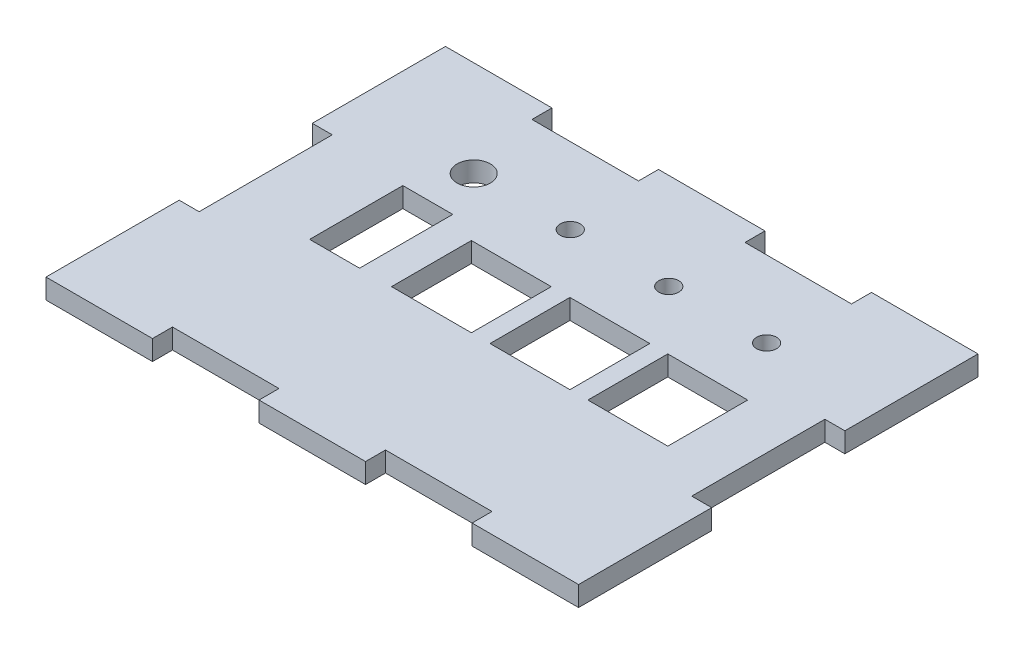
SolidWorks part; units mm, degrees
ref_plane "Front Plane" through (0, 0, 0) normal (0, 0, 1) x (1, 0, 0)
ref_plane "Top Plane" through (0, 0, 0) normal (0, 1, 0) x (1, 0, 0)
ref_plane "Right Plane" through (0, 0, 0) normal (1, 0, 0) x (0, 0, -1)
sketch "Top and Bottom" plane through (0, 0, 0) normal (0, 1, 0) x (1, 0, 0)
  line L0 (32, 60) -> (48, 60)
  line L1 (0, 0) -> (16, 0)
  line L2 (0, 0) -> (0, 20)
  line L3 (0, 60) -> (16, 60)
  line L4 (80, 0) -> (80, 20)
  line L5 (64, 60) -> (80, 60)
  line L6 (16, 60) -> (16, 57)
  line L7 (16, 57) -> (32, 57)
  line L8 (32, 60) -> (32, 57)
  line L9 (42, 36.7) -> (54, 36.7)
  line L10 (48, 60) -> (48, 57)
  line L11 (48, 57) -> (64, 57)
  line L12 (64, 60) -> (64, 57)
  line L13 (27.2, 36.7) -> (39.2, 36.7)
  line L14 (64, 0) -> (64, 3)
  line L15 (48, 3) -> (64, 3)
  line L16 (48, 0) -> (48, 3)
  line L17 (32, 0) -> (32, 3)
  line L18 (16, 0) -> (16, 3)
  line L19 (16, 3) -> (32, 3)
  line L20 (64, 0) -> (80, 0)
  line L21 (32, 0) -> (48, 0)
  line L22 (0, 40) -> (0, 60)
  line L23 (0, 40) -> (3, 40)
  line L24 (80, 40) -> (77, 40)
  line L25 (0, 20) -> (3, 20)
  line L26 (3, 40) -> (3, 20)
  line L27 (77, 40) -> (77, 20)
  line L28 (80, 20) -> (77, 20)
  line L29 (80, 40) -> (80, 60)
  line L30 (27.2, 36.7) -> (27.2, 24.7)
  line L31 (27.2, 24.7) -> (39.2, 24.7)
  line L32 (39.2, 36.7) -> (39.2, 24.7)
  line L33 (42, 36.7) -> (42, 24.7)
  line L34 (42, 24.7) -> (54, 24.7)
  line L35 (54, 36.7) -> (54, 24.7)
  line L36 (56.7, 36.7) -> (68.7, 36.7)
  line L37 (56.7, 36.7) -> (56.7, 24.7)
  line L38 (56.7, 24.7) -> (68.7, 24.7)
  line L39 (68.7, 36.7) -> (68.7, 24.7)
  line L41 (14.9, 38.7) -> (22.4, 38.7)
  line L42 (14.9, 38.7) -> (14.9, 24.7)
  line L43 (14.9, 24.7) -> (22.4, 24.7)
  line L44 (22.4, 38.7) -> (22.4, 24.7)
  circle A0 centre (33.2, 45.55) radius 1.5
  circle A1 centre (48, 45.55) radius 1.5
  circle A2 centre (62.7, 45.55) radius 1.5
  circle A3 centre (18.65, 45.6) radius 2.5
  dimension "D16" = 3
  dimension "D18" = 6
  dimension "D20" = 3
  dimension "D21" = 3
  dimension "D22" = 2.7
  dimension "D28" = 5
  dimension "D29" = 6.9
  dimension "D1" = 60
  dimension "D2" = 80
  dimension "D3" = 3
  dimension "D4" = 16
  dimension "D5" = 16
  dimension "D6" = 16
  dimension "D7" = 3
  dimension "D8" = 16
  dimension "D9" = 12
  dimension "D10" = 3
  dimension "D11" = 20
  dimension "D12" = 20
  dimension "D13" = 12
  dimension "D14" = 20.3
  dimension "D15" = 3
  dimension "D17" = 6
  dimension "D19" = 6
  dimension "D23" = 2.8
  dimension "D24" = 8.3
  dimension "D25" = 7.5
  dimension "D26" = 14
  dimension "D27" = 0
  dimension "D30" = 8.85
  dimension "D31" = 8.85
  dimension "D32" = 3.75
  dimension "D33" = 8.85
  dimension "D34" = 12
  dimension "D35" = 12
  dimension "D36" = 12
  dimension "D37" = 12
  dimension "D38" = 3
  dimension "D39" = 4.8
  dimension "D40" = 20
  dimension "D41" = 20
extrude "Top and Bottom Extruded" add sketch "Top and Bottom" along normal blind 3
